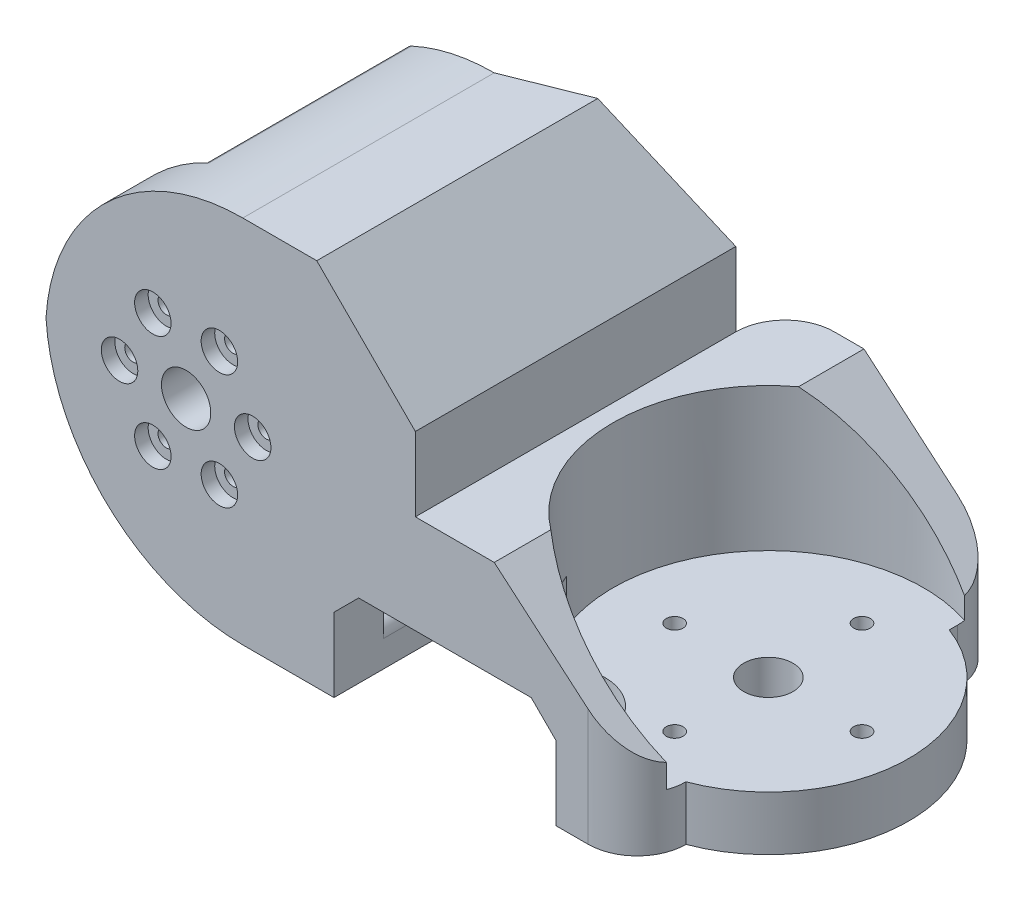
SolidWorks part; units mm, degrees
ref_plane "前视基准面" through (0, 0, 0) normal (0, 0, 1) x (1, 0, 0)
ref_plane "上视基准面" through (0, 0, 0) normal (0, 1, 0) x (1, 0, 0)
ref_plane "右视基准面" through (0, 0, 0) normal (1, 0, 0) x (0, 0, -1)
sketch "草图1" plane through (0, 0, 0) normal (0, 1, 0) x (1, 0, 0)
  line L1 (-70, 37.5) -> (70, 37.5)
  line L2 (-70, 37.5) -> (-70, -37.5)
  line L3 (-70, -37.5) -> (70, -37.5)
  line L4 (70, 37.5) -> (70, -37.5)
  line L5 (-70, 37.5) -> (70, -37.5) construction
  line L6 (-70, -37.5) -> (70, 37.5) construction
  point P0 (0, 0)
  dimension "D1" = 140
  dimension "D2" = 75
extrude "凸台-拉伸1" add sketch "草图1" along normal blind 75
sketch "草图2" plane through (0, 0, -37.5) normal (0, 0, -1) x (-1, 0, 0)
  line L0 (66.851, 37.5) -> (-74.6143, 37.5) construction
  line L2 (70, 75) -> (70, 0) construction
  circle A0 centre (41.5, 37.5) radius 13.5 construction
  circle A1 centre (41.5, 37.5) radius 5
  circle A2 centre (55, 37.5) radius 1.7
  circle A3 centre (48.25, 25.8087) radius 1.7
  circle A4 centre (34.75, 25.8087) radius 1.7
  circle A5 centre (28, 37.5) radius 1.7
  circle A6 centre (34.75, 49.1913) radius 1.7
  circle A7 centre (48.25, 49.1913) radius 1.7
  point P22 (41.5, 37.5)
  dimension "D1" = 28.5
  dimension "D2" = 10
  dimension "D3" = 3.4
  dimension "D5" = 27
  dimension "D4" = 6
extrude "切除-拉伸3" cut sketch "草图2" against normal blind 75
sketch "草图3" plane through (0, 0, -37.5) normal (0, 0, -1) x (-1, 0, 0)
  circle A0 centre (41.5, 37.5) radius 30
  dimension "D1" = 60
extrude "切除-拉伸4" cut sketch "草图3" against normal offset from surface (65 mm away) 10 up to face at (-49.95, 49.1913, 37.5)
sketch "草图5" plane through (-70, 0, 0) normal (-1, 0, 0) x (0, 0, 1)
  line L0 (-37.5, 28.1325) -> (-37.5, 0) construction
  line L1 (-13.5, 102.7561) -> (-99.6108, 102.7561)
  line L2 (-13.5, 102.7561) -> (-13.5, -25.0605)
  line L3 (-13.5, -25.0605) -> (-99.6108, -25.0605)
  line L4 (-99.6108, 102.7561) -> (-99.6108, -25.0605)
  dimension "D1" = 24
extrude "切除-拉伸5" cut sketch "草图5" against normal blind 65
sketch "草图6" plane through (0, 75, 0) normal (0, 1, 0) x (1, 0, 0)
  line L0 (-65.9606, -0.9) -> (85.2628, -0.9) construction
  line L2 (-70, -37.5) -> (70, -37.5) construction
  line L3 (-70, 13.5) -> (-70, -37.5) construction
  circle A0 centre (40, -0.9) radius 19 construction
  circle A1 centre (40, -0.9) radius 5
  circle A2 centre (59, -0.9) radius 1.7
  circle A3 centre (40, -19.9) radius 1.7
  circle A4 centre (21, -0.9) radius 1.7
  circle A5 centre (40, 18.1) radius 1.7
  point P18 (40, -0.9)
  dimension "D2" = 3.4
  dimension "D3" = 10
  dimension "D4" = 38
  dimension "D6" = 110
  dimension "D1" = 36.6
  dimension "D5" = 4
extrude "切除-拉伸6" cut sketch "草图6" against normal through all
sketch "草图7" plane through (0, 75, 0) normal (0, 1, 0) x (1, 0, 0)
  circle A0 centre (40, -0.9) radius 31.5
  dimension "D1" = 63
extrude "切除-拉伸8" cut sketch "草图7" against normal offset from surface (64 mm away) 11 contours A0 up to face at (40, 0, -16.4)
sketch "草图8" plane through (0, 75, 0) normal (0, 1, 0) x (1, 0, 0)
  line L1 (5, 60.8483) -> (86.6072, 60.8483)
  line L2 (5, 60.8483) -> (5, -41.1109)
  line L3 (5, -41.1109) -> (86.6072, -41.1109)
  line L4 (86.6072, 60.8483) -> (86.6072, -41.1109)
  circle A0 centre (40, -0.9) radius 5 construction
  dimension "D1" = 35
extrude "切除-拉伸9" cut sketch "草图8" against normal blind 35
sketch "草图9" plane through (0, 0, -13.5) normal (0, 0, -1) x (-1, 0, 0)
  line L0 (5, 0) -> (5, 75) construction
  line L1 (5, 67.5) -> (93.1549, 67.5)
  line L2 (5, 67.5) -> (5, 7.5)
  line L3 (5, 7.5) -> (93.1549, 7.5)
  line L4 (93.1549, 67.5) -> (93.1549, 7.5)
extrude "切除-拉伸10" cut sketch "草图9" against normal offset from surface (41 mm away) 10 up to face at (-49.95, 49.1913, 37.5)
sketch "草图10" plane through (0, 0, 37.5) normal (0, 0, 1) x (1, 0, 0)
  line L0 (-70, 0) -> (70, 0) construction
  line L1 (-11.5, 20) -> (33.5, 20)
  line L2 (-11.5, 20) -> (-11.5, -30)
  line L3 (-11.5, -30) -> (33.5, -30)
  line L4 (33.5, 20) -> (33.5, -30)
  circle A0 centre (-41.5, 37.5) radius 5 construction
  dimension "D1" = 30
  dimension "D2" = 50
  dimension "D3" = 20
  dimension "D4" = 45
extrude "切除-拉伸11" cut sketch "草图10" against normal blind 20
fillet "圆角2" radius 10 1 edges at (33.5, 5.5, 17.5)
sketch "草图11" plane through (0, 0, -37.5) normal (0, 0, -1) x (-1, 0, 0)
  line L1 (-82.4623, 20) -> (-50, 20)
  line L2 (-82.4623, 20) -> (-82.4623, -2.5192)
  line L3 (-82.4623, -2.5192) -> (-50, -2.5192)
  line L4 (-50, 20) -> (-50, -2.5192)
  line L5 (-70, 0) -> (5, 0) construction
  line L6 (-70, 40) -> (-70, 0) construction
  dimension "D1" = 20
  dimension "D2" = 20
sketch "草图12" plane through (0, 40, 0) normal (0, 1, 0) x (1, 0, 0)
  line L0 (82.4623, 37.5) -> (50, 37.5) construction
  line L1 (70, -37.5) -> (55, -37.5)
  line L2 (70, -37.5) -> (70, 37.5)
  line L3 (70, 37.5) -> (55, 37.5)
  line L4 (55, -37.5) -> (55, 37.5)
  dimension "D1" = 15
extrude "切除-拉伸13" cut sketch "草图12" against normal up to surface (29 mm away) up to face at (39.1774, 11, 11.4788)
sketch "草图13" plane through (0, 0, 37.5) normal (0, 0, 1) x (1, 0, 0)
  line L0 (21, 40) -> (55, 11)
  line L1 (5, 40) -> (55, 40) construction
  line L2 (55, 11) -> (55, 40)
  line L3 (55, 40) -> (21, 40)
  line L4 (5, 40) -> (5, 75) construction
  dimension "D1" = 16
extrude "切除-拉伸14" cut sketch "草图13" against normal blind 90
sketch "草图14" plane through (0, 0, 0) normal (0, -1, 0) x (1, 0, 0)
  line L0 (50, -25.788) -> (50, -49.0432)
  line L1 (50, 45.4705) -> (107.0005, 45.4705)
  line L2 (50, 45.4705) -> (50, 27.588)
  line L3 (50, -49.0432) -> (107.0005, -49.0432)
  line L4 (107.0005, 45.4705) -> (107.0005, -49.0432)
  arc A0 (50, -25.788) -> (50, 27.588) centre (40, 0.9) ccw
  dimension "D1" = 57
  dimension "D2" = 10
extrude "切除-拉伸15" cut sketch "草图14" against normal blind 20
chamfer "倒角1" distance 5 angle 45 2 edges at (-11.5, 20, 32.5) (33.5, 20, 34.611)
chamfer "倒角2" distance 5 angle 45 1 edges at (-5, 20, 22.5)
chamfer "倒角3" distance 5 angle 45 1 edges at (13.2289, 15.5, 17.5) first distance on face at (30.2699, 19.142, 11.2364)
chamfer "倒角4" distance 25 angle 45 2 edges at (-5, 3.75, -13.5) (-5, 71.25, -13.5)
sketch "草图18" plane through (0, 75, 0) normal (0, 1, 0) x (1, 0, 0)
  line L0 (5, 37.5) -> (-30, 13.5)
  line L1 (-30, 13.5) -> (-17.0828, 37.6969)
  line L2 (-17.0828, 37.6969) -> (5, 37.5)
extrude "切除-拉伸16" cut sketch "草图18" against normal blind 90
fillet "圆角4" radius 40 2 edges at (-70, 0, 12) (-70, 75, 12)
fillet "圆角9" radius 10 2 edges at (50, 7.6324, -37.5) (50, 7.6324, 37.5)
sketch "草图19" plane through (0, 75, 0) normal (0, 1, 0) x (1, 0, 0)
  line L0 (-30, 13.5) -> (5, 27.5)
  line L1 (5, 37.5) -> (5, -37.5) construction
  line L2 (5, 27.5) -> (5, 42.6655)
  line L3 (5, 42.6655) -> (-30, 13.5)
  line L4 (21, 37.5) -> (5, 37.5) construction
  dimension "D1" = 10
extrude "切除-拉伸17" cut sketch "草图19" against normal blind 90
fillet "圆角10" radius 10 1 edges at (5, 20, -37.5)
fillet "圆角11" radius 2 2 edges at (-53.3184, 7.5, 7) (-53.3184, 67.5, 7)
fillet "圆角12" radius 15 2 edges at (-5, 7.5, -3) (-5, 67.5, 2)
chamfer "倒角5" distance 20 angle 45 1 edges at (5, 75, 5)
fillet "圆角13" radius 3 3 edges at (-11.5, 10.1408, 22.5) (-6.7241, 15.5179, 17.5) (-5, 23.75, 17.5)
sketch "草图20" plane through (0, 0, 37.5) normal (0, 0, 1) x (1, 0, 0)
  circle A0 centre (-34.75, 49.1913) radius 3.7
  circle A1 centre (-48.25, 49.1913) radius 3.7
  circle A2 centre (-55, 37.5) radius 3.7
  circle A3 centre (-48.25, 25.8087) radius 3.7
  circle A4 centre (-34.75, 25.8087) radius 3.7
  circle A5 centre (-28, 37.5) radius 3.7
  point P16 (-41.5, 37.5)
  dimension "D1" = 7.4
  dimension "D2" = 6
extrude "切除-拉伸18" cut sketch "草图20" against normal offset from surface (2.75 mm away) 7.25 up to face at (-25.6258, 29.4644, 27.5)
sketch "草图21" plane through (0, 0, 0) normal (0, -1, 0) x (1, 0, 0)
  circle A0 centre (40, -18.1) radius 3.7
  circle A1 centre (21, 0.9) radius 3.7
  circle A2 centre (40, 19.9) radius 3.7
  circle A3 centre (59, 0.9) radius 3.7
  point P12 (40, 0.9)
  dimension "D1" = 7.4
  dimension "D2" = 4
extrude "切除-拉伸19" cut sketch "草图21" against normal offset from surface (5.5 mm away) 5.5 up to face at (59, 11, 2.6)
ref_point "点1"
sketch "草图22" plane through (0, 0, 27.5) normal (0, 0, -1) x (-1, 0, 0)
  circle A0 centre (41.5, 37.5) radius 28
  circle A1 centre (41.5, 37.5) radius 5
  circle A2 centre (48.25, 49.1913) radius 1.7
  circle A3 centre (34.75, 49.1913) radius 1.7
  circle A4 centre (28, 37.5) radius 1.7
  circle A5 centre (34.75, 25.8087) radius 1.7
  circle A6 centre (48.25, 25.8087) radius 1.7
  circle A7 centre (55, 37.5) radius 1.7
  dimension "D1" = 56
extrude "凸台-拉伸2" add sketch "草图22" along normal blind 7.25
